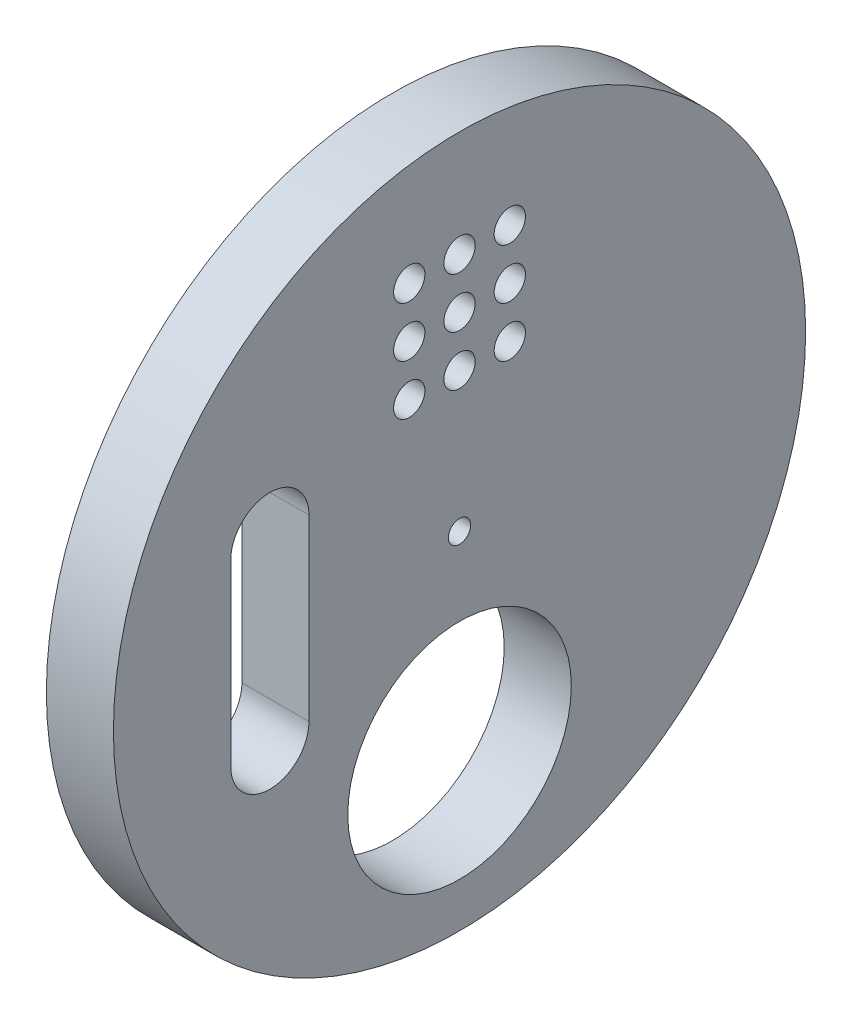
SolidWorks part; units mm, degrees
ref_plane "Front Plane" through (0, 0, 0) normal (0, 0, 1) x (1, 0, 0)
ref_plane "Top Plane" through (0, 0, 0) normal (0, 1, 0) x (1, 0, 0)
ref_plane "Right Plane" through (0, 0, 0) normal (1, 0, 0) x (0, 0, -1)
sketch "Sketch1" plane through (0, 0, 0) normal (1, 0, 0) x (0, 0, -1)
  line L1 (-56.25, -119) -> (56.25, -119)
  line L2 (-56.25, -119) -> (-56.25, 119)
  line L3 (-56.25, 119) -> (56.25, 119)
  line L4 (56.25, -119) -> (56.25, 119)
  line L5 (-56.25, -119) -> (56.25, 119) construction
  line L6 (-56.25, 119) -> (56.25, -119) construction
  point P0 (0, 0)
  dimension "D1" = 238
  dimension "D2" = 112.5
extrude "Boss-Extrude1" add sketch "Sketch1" along normal blind 6
sketch "Sketch2" plane through (6, 0, 0) normal (1, 0, 0) x (0, 0, -1)
  line L0 (0, -119) -> (0, -99) construction
  line L1 (0, -82.0294) -> (30.9706, -113) construction
  line L4 (56.25, -119) -> (56.25, 119)
  line L5 (56.25, 119) -> (-56.25, 119)
  line L6 (-56.25, 119) -> (-56.25, -119)
  line L7 (-56.25, -119) -> (56.25, -119)
  line L8 (56.25, -119) -> (56.25, 119) construction
  line L9 (56.25, 119) -> (-56.25, 119) construction
  line L10 (-56.25, 119) -> (-56.25, -119) construction
  line L11 (-56.25, -119) -> (56.25, -119) construction
  line L12 (0, -99) -> (0, -82.0294) construction
  line L13 (30.9706, -113) -> (0, -113) construction
  line L14 (0, -82.0294) -> (30.9706, -82.0294) construction
  line L15 (30.9706, -82.0294) -> (30.9706, -113) construction
  line L16 (0, -113) -> (0, -109) construction
  line L17 (8.4853, -90.5147) -> (7.0711, -91.9289) construction
  line L18 (0, -82.0294) -> (-16.9706, -82.0294) construction
  line L19 (-16.9706, -82.0294) -> (0, -65.0589) construction
  line L20 (0, -65.0589) -> (0, -82.0294) construction
  line L21 (0, -65.0589) -> (16.9706, -82.0294) construction
  line L22 (16.9706, -82.0294) -> (0, -99) construction
  line L23 (0, -99) -> (-16.9706, -82.0294) construction
  line L24 (-16.9706, -74.0294) -> (-16.9706, -90.0294) construction
  line L25 (-13.4706, -74.0294) -> (-13.4706, -90.0294)
  line L26 (-20.4706, -74.0294) -> (-20.4706, -90.0294)
  line L27 (0, -65.0589) -> (0, -60.5589) construction
  line L28 (0, -60.5589) -> (-4.5, -60.5589) construction
  line L29 (-4.5, -60.5589) -> (-4.5, -65.0589) construction
  circle A2 centre (0, -82.0294) radius 30.9706
  circle A3 centre (0, -99) radius 10
  circle A4 centre (-16.9706, -82.0294) radius 10 construction
  circle A5 centre (0, -65.0589) radius 10 construction
  arc A7 (-13.4706, -74.0294) -> (-20.4706, -74.0294) centre (-16.9706, -74.0294) ccw
  arc A8 (-20.4706, -90.0294) -> (-13.4706, -90.0294) centre (-16.9706, -90.0294) ccw
  circle A10 centre (-4.5, -60.5589) radius 1.4
  circle A11 centre (0, -60.5589) radius 1.4
  circle A12 centre (4.5, -60.5589) radius 1.4
  circle A15 centre (0, -65.0589) radius 1.4
  circle A16 centre (4.5, -65.0589) radius 1.4
  circle A19 centre (0, -69.5589) radius 1.4
  circle A20 centre (4.5, -69.5589) radius 1.4
  circle A31 centre (-4.5, -65.0589) radius 1.4
  circle A32 centre (-4.5, -69.5589) radius 1.4
  circle A35 centre (0, -82.0294) radius 1
  point P19 (-16.9706, -82.0294)
  dimension "D2" = 20
  dimension "D8" = 2.8
  dimension "D12" = 4.5
  dimension "D14" = 2
  dimension "D3" = 6
  dimension "D4" = 2
  dimension "D5" = 4
  dimension "D6" = 7
  dimension "D7" = 16
  dimension "D9" = 4.5
  dimension "D13" = 4.5
  dimension "D1" = 0
  dimension "D10" = 3
  dimension "D11" = 3
extrude "Boss-Extrude2" add sketch "Sketch2" along normal blind 6
sketch "Sketch3" plane through (0, 0, 0) normal (-1, 0, 0) x (0, 0, 1)
  line L4 (-56.25, 119) -> (-56.25, -119)
  line L5 (-56.25, -119) -> (56.25, -119)
  line L6 (56.25, -119) -> (56.25, 119)
  line L7 (56.25, 119) -> (-56.25, 119)
  line L8 (-56.25, 119) -> (-56.25, -119)
  line L9 (-56.25, -119) -> (56.25, -119)
  line L10 (56.25, -119) -> (56.25, 119)
  line L11 (56.25, 119) -> (-56.25, 119)
  dimension "D1" = 0
extrude "Cut-Extrude1" cut sketch "Sketch3" against normal blind 6
